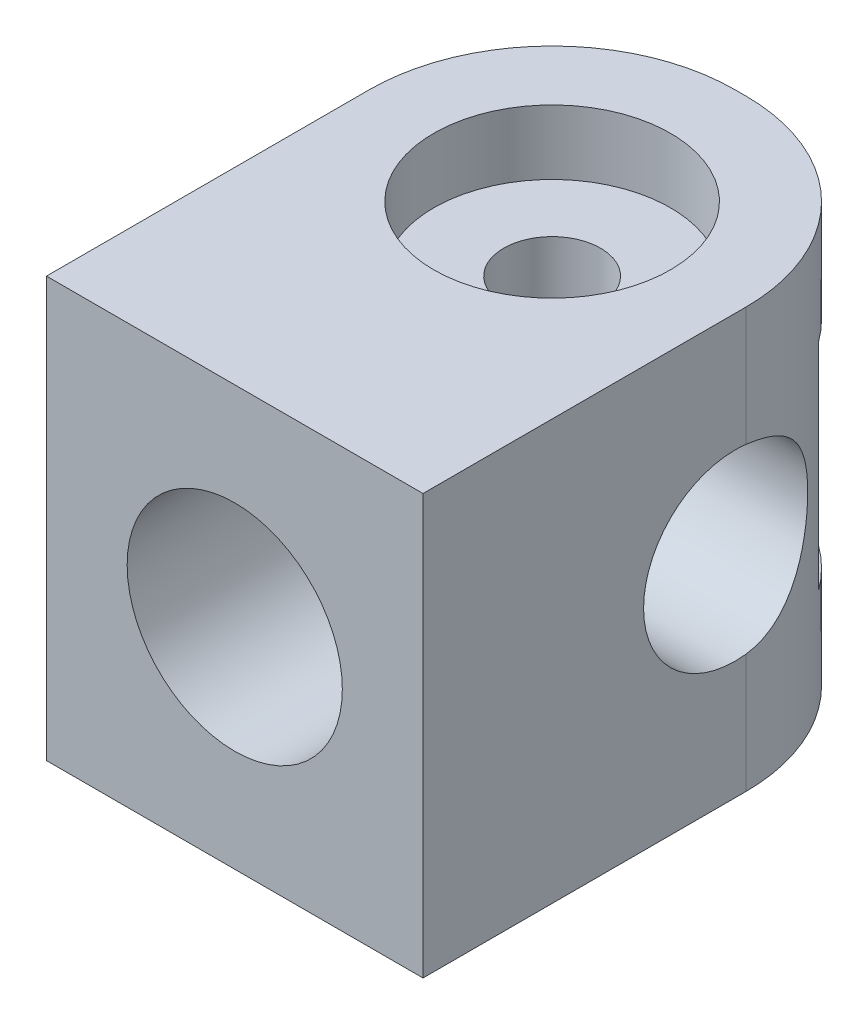
SolidWorks part; units mm, degrees
ref_plane "Plan de face" through (0, 0, 0) normal (0, 0, 1) x (1, 0, 0)
ref_plane "Plan de dessus" through (0, 0, 0) normal (0, 1, 0) x (1, 0, 0)
ref_plane "Plan de droite" through (0, 0, 0) normal (1, 0, 0) x (0, 0, -1)
sketch "Esquisse1" plane through (0, 0, 0) normal (0, 0, 1) x (1, 0, 0)
  line L1 (0, 0) -> (35, 0)
  line L2 (0, 0) -> (0, -39)
  line L3 (0, -39) -> (35, -39)
  line L4 (35, 0) -> (35, -39)
  dimension "D1" = 35
  dimension "D2" = 39
extrude "Boss.-Extru.1" add sketch "Esquisse1" along normal blind 47
sketch "Esquisse2" plane through (0, 0, 47) normal (0, 0, 1) x (1, 0, 0)
  line L0 (0, 0) -> (35, -39)
  circle A0 centre (17.5, -19.5) radius 10
extrude "Enlèv. mat.-Extru.1" cut sketch "Esquisse2" against normal blind 20 contours L0 A0 | L0 A0 region at (20.6587, -16.6653, 47) region at (14.3413, -22.3347, 47)
fillet "Congé1" radius 17 2 edges at (0, -19.5, 0) (35, -19.5, 0)
sketch "Esquisse3" plane through (0, 0, 0) normal (0, 0, -1) x (-1, 0, 0)
  line L0 (-35, -39) -> (-35, -29.5)
  line L1 (0, 0) -> (0, -39) construction
  line L2 (-35, -29.5) -> (0, -29.5)
  line L3 (-35, -29.5) -> (-35, -9.5)
  line L4 (-35, -9.5) -> (0, -9.5)
  line L5 (0, -29.5) -> (0, -9.5)
  line M5 (-17, -39) -> (-17, 0)
  line M7 (-18, 0) -> (-18, -39)
  dimension "D1" = 9.5
  dimension "D2" = 20
extrude "Enlèv. mat.-Extru.2" cut sketch "Esquisse3" against normal blind 7 contours L4 L2 M7 M5 | L4 L3 L2 M7 | L2 L5 L4 M5 region at (26.5, -19.5, 0) region at (17.5, -19.5, 0) region at (8.5, -19.5, 0)
sketch "Esquisse4" plane through (35, 0, 0) normal (1, 0, 0) x (0, 0, -1)
  line L0 (-47, -39) -> (-18, -39)
  line L1 (-47, -39) -> (-17, -39) construction
  line L2 (-18, -39) -> (-18, 0)
  line L3 (-47, 0) -> (-17, 0) construction
  circle A0 centre (-18, -19.5) radius 8.5
  line M3 (-17, -39) -> (-17, 0)
  dimension "D2" = 17
  dimension "D1" = 29
extrude "Enlèv. mat.-Extru.3" cut sketch "Esquisse4" against normal blind 29 contours L2 A0 | A0 M3 | L2 A0 M3 region at (35, -19.5, 21.6075) region at (35, -19.5, 17.5006) region at (35, -19.5, 13.8464)
sketch "Esquisse5" plane through (0, 0, 0) normal (0, 1, 0) x (1, 0, 0)
  line L0 (17.5, -47) -> (17.5, -17.5)
  line L1 (35, -47) -> (0, -47) construction
  circle A0 centre (17.5, -17.5) radius 4.5
  circle A1 centre (17.5, -17.5) radius 11
  dimension "D1" = 9
  dimension "D2" = 29.5
extrude "Enlèv. mat.-Extru.4" cut sketch "Esquisse5" against normal through all contours A0 region at (14.408, 0, 14.408)
sketch "Esquisse7" plane through (0, 0, 0) normal (0, 1, 0) x (1, 0, 0)
  circle A0 centre (17.5, -17.5) radius 11
extrude "Enlèv. mat.-Extru.5" cut sketch "Esquisse7" against normal blind 6
sketch "Esquisse8" plane through (0, -39, 0) normal (0, -1, 0) x (1, 0, 0)
  circle A0 centre (17.5, 17.5) radius 11
extrude "Enlèv. mat.-Extru.6" cut sketch "Esquisse8" against normal blind 6
sketch "Esquisse10" plane through (0, 0, 0) normal (-1, 0, 0) x (0, 0, 1)
  circle A0 centre (18, -19.5) radius 4.5
  circle A1 centre (18, -19.5) radius 8.5
  circle A2 centre (18, -19.5) radius 8.5
  line M3 (17, 0) -> (17, -39)
  dimension "D2" = 9
  dimension "D1" = 0
extrude "Enlèv. mat.-Extru.7" cut sketch "Esquisse10" against normal blind 6 contours A0 M3 | A0 M3 region at (0, -19.5, 19.3823) region at (0, -19.5, 15.5394)
